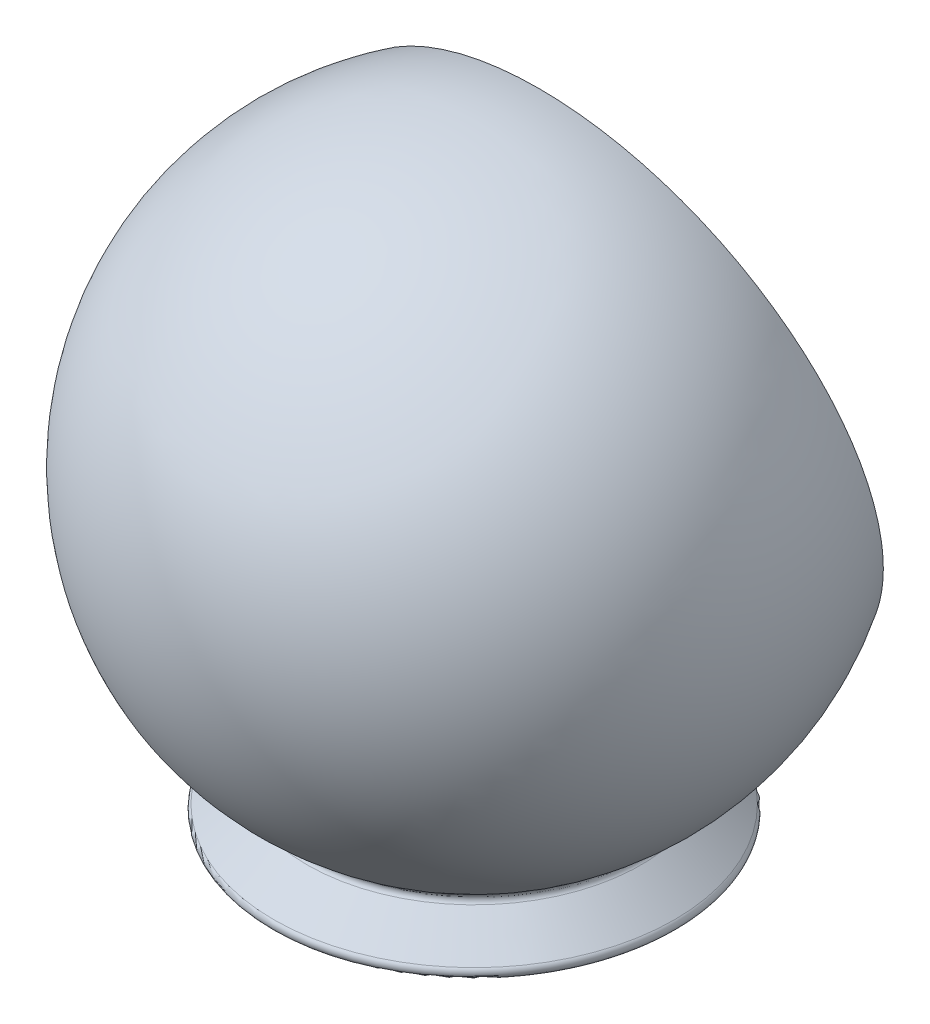
SolidWorks part; units mm, degrees
ref_plane "Front Plane" through (0, 0, 0) normal (0, 0, 1) x (1, 0, 0)
ref_plane "Top Plane" through (0, 0, 0) normal (0, 1, 0) x (1, 0, 0)
ref_plane "Right Plane" through (0, 0, 0) normal (1, 0, 0) x (0, 0, -1)
sketch "Base_sketch" plane through (0, 0, 0) normal (0, 1, 0) x (1, 0, 0)
  line L0 (0, 63.5) -> (0, -63.5)
  line L2 (0, -69.85) -> (0, 69.85) construction
  arc A0 (0, 63.5) -> (0, -63.5) centre (0, 0) cw
  point P7 (0, 0)
  dimension "D2" = 63.5
  dimension "D1" = 127
revolve "Revolve2" add sketch "Base_sketch" angle 360 about L0
ref_plane "Plane3" through (0, -48.26, 0) normal (0, 1, 0) x (1, 0, 0)
ref_plane "Plane4" through (0, -63.5, 0) normal (0, 1, 0) x (1, 0, 0)
sketch "Sketch8" plane through (0, -48.26, 0) normal (0, 1, 0) x (1, 0, 0)
  circle A0 centre (0, 0) radius 27.942
  dimension "D1" = 55.884
sketch "Sketch9" plane through (0, -63.5, 0) normal (0, 1, 0) x (1, 0, 0)
  circle A0 centre (0, 0) radius 44.45
  dimension "D1" = 88.9
loft "Loft1" add profiles "Sketch8", "Sketch9" connector at (-15.5018, -48.26, -23.2476) connector at (-25.1198, -63.5, -36.6715)
combine bodies "Combine1" operation type add bodies to combine 105 104
fillet "Fillet2" radius 1.27 1 edges at (0, -53.7209, 33.8573)
fillet "Fillet3" radius 1.27 1 edges at (0, -63.5, 44.45)
sketch "Sketch10" plane through (0, -48.26, 0) normal (0, 1, 0) x (1, 0, 0)
  line L0 (37.2305, 41.1538) -> (-37.2305, 41.1538)
  circle A0 centre (0, 0) radius 41.1538
  point P6 (0, 41.1538)
ref_plane "Plane5" through (0, 6.8358, -27.4169) normal (0, 0.2419, -0.9703) x (-1, 0, 0)
sketch "Sketch11" plane through (0, 6.8358, -27.4169) normal (0, 0.2419, -0.9703) x (-1, 0, 0)
  line L1 (-68.0843, 65.2783) -> (67.1582, 65.2783)
  line L2 (-68.0843, 65.2783) -> (-68.0843, -59.9167)
  line L3 (-68.0843, -59.9167) -> (67.1582, -59.9167)
  line L4 (67.1582, 65.2783) -> (67.1582, -59.9167)
sketch "Sketch12" plane through (0, 6.8358, -27.4169) normal (0, 0.2419, -0.9703) x (-1, 0, 0)
  line L0 (0, 57.3739) -> (0, -56.7825) construction
  line L1 (57.3739, 0) -> (-57.3739, 0) construction
  circle A0 centre (0, 0) radius 57.3739
  circle A1 centre (0, 0) radius 51.5188
  dimension "D1" = 114.7478
  dimension "D2" = 103.0375
extrude "Cut-Extrude1" cut sketch "Sketch12" along normal blind 38.1 contours A1 | A0 A1 region at (55.7511, 6.8358, -27.4169) region at (0, 6.8358, -27.4169)
extrude "Cut-Extrude2" cut sketch "Sketch12<3>" against normal blind 1.27 contours A1
sketch "Sketch12<3>" plane through (0, 6.8358, -27.4169) normal (0, 0.2419, -0.9703) x (-1, 0, 0) same geometry as "Sketch12"
sketch "Sketch17" plane through (0, 6.5286, -26.1846) normal (0, 0.2419, -0.9703) x (-1, 0, 0)
  text T0 "<b>7:02AM</b>" font "Nirmala UI" height in points 48
extrude "Boss-Extrude2" add sketch "Sketch17" along normal blind 0.0127
sketch "Sketch19" plane through (0, 6.5286, -26.1846) normal (0, 0.2419, -0.9703) x (-1, 0, 0)
  line L0 (271.2329, 395.0841) -> (1123.8995, 395.0841) construction
  line L1 (0, 51.5188) -> (0, -50.7587) construction
  line L3 (-31.2285, -40.9752) -> (31.2285, -40.9752) construction
  circle A0 centre (0, 0) radius 51.5188 construction
  circle A4 centre (0, 0) radius 35.3296 construction
  circle A5 centre (0, -35.3296) radius 8.2099
  circle A6 centre (19.4616, -29.486) radius 8.2635
  circle A7 centre (32.4853, -13.8884) radius 8.3061
  circle A8 centre (-32.4853, -13.8884) radius 8.3061
  circle A9 centre (-19.4616, -29.486) radius 8.2635
  point P18 (0, 0)
  point P19 (0, 0)
  point P20 (16.2418, -38.3848)
  point P21 (0, 0)
  point P22 (19.561, -36.8043)
  dimension "D1" = 70.6592
  dimension "D2" = 20.32
  dimension "D3" = 20.32
extrude "Boss-Extrude3" add sketch "Sketch19" along normal blind 0.0127 contours A5 | A9 | A8 | A6 | A7
sketch "Sketch21" plane through (0, 6.5286, -26.1846) normal (0, 0.2419, -0.9703) x (-1, 0, 0)
  line L0 (81.7132, 272.3369) -> (465.0465, 272.3369) construction
